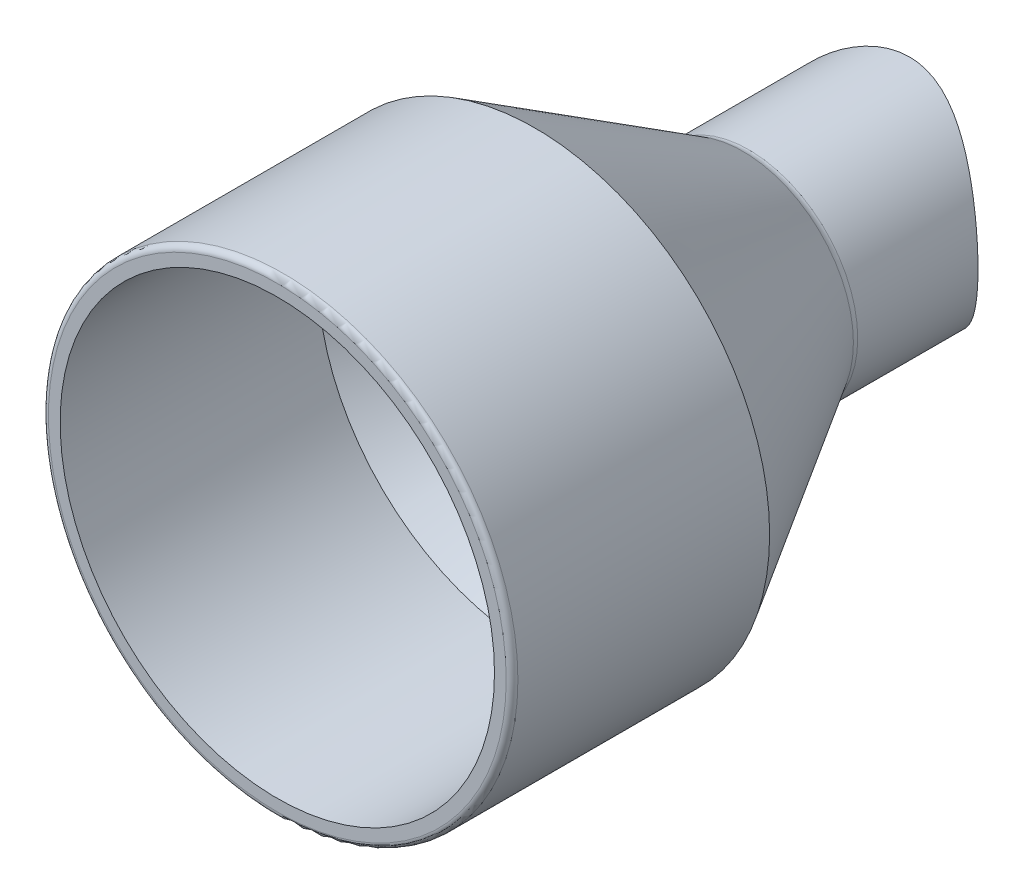
SolidWorks part; units mm, degrees
ref_plane "Front Plane" through (0, 0, 0) normal (0, 0, 1) x (1, 0, 0)
ref_plane "Top Plane" through (0, 0, 0) normal (0, 1, 0) x (1, 0, 0)
ref_plane "Right Plane" through (0, 0, 0) normal (1, 0, 0) x (0, 0, -1)
sketch "Sketch1" plane through (0, 0, 0) normal (0, 0, 1) x (1, 0, 0)
  circle A0 centre (0, 0) radius 20.05
  circle A1 centre (0, 0) radius 18.55
  dimension "D1" = 40.1
  dimension "D2" = 1.5
extrude "Boss-Extrude1" add sketch "Sketch1" along normal blind 22
sketch "Sketch2" plane through (0, 0, 0) normal (0, 0, -1) x (-1, 0, 0)
  circle A0 centre (0, 0) radius 20.05 construction
  point P0 (0, 0)
  point P1 (0, 20.05)
sketch "Sketch4" plane through (0, 0, 22) normal (0, 0, 1) x (1, 0, 0)
  point P0 (0, 20.05)
ref_plane "Plane1" through (0, 0, 0) normal (1, 0, 0) x (0, 0, -1)
sketch "Sketch5" plane through (0, 0, 0) normal (1, 0, 0) x (0, 0, -1)
  line L0 (0, 0) -> (30, 0) construction
  line L3 (18, 9.3) -> (0, 20.05)
  line L4 (0, -20.05) -> (0, 20.05) construction
  line L5 (0, 20.05) -> (0, 18.55)
  line L6 (0, 18.55) -> (18, 7.8)
  line L7 (18, 7.8) -> (18, 9.3)
  line L10 (18, 9.3) -> (32, 9.3)
  line L11 (18, 9.3) -> (18, 7.8)
  line L12 (18, 7.8) -> (32, 7.8)
  line L13 (32, 9.3) -> (32, 7.8)
  dimension "D1" = 18
  dimension "D2" = 14
  dimension "D4" = 1.5
  dimension "5.9" = 7.8
fillet "Fillet1" radius 0.5 1 edges at (20.05, 0, 22)
revolve "Revolve1" add sketch "Sketch5" angle 360 about L0 region at (0, 13.925, -9) region at (0, 8.55, -25)
sketch "Sketch6" plane through (0, 0, 0) normal (1, 0, 0) x (0, 0, -1)
  line L2 (32, 9.3) -> (32, -9.3) construction
  circle A0 centre (42.7969, 0) radius 14.25
  point P5 (32, 0)
  dimension "D1" = 28.5
extrude "Cut-Extrude1" cut sketch "Sketch6" against normal blind 10 and the other way blind 10
sketch "Sketch7" plane through (0, 0, 22) normal (0, 0, 1) x (1, 0, 0)
  line L1 (-6.3, -1) -> (-9.3, -1)
  line L2 (-6.3, -1) -> (-6.3, 1)
  line L3 (-6.3, 1) -> (-9.3, 1)
  line L4 (-9.3, -1) -> (-9.3, 1)
  line L5 (-6.3, -1) -> (-9.3, 1) construction
  line L6 (-6.3, 1) -> (-9.3, -1) construction
  line L7 (6.3, -1) -> (9.3, -1)
  line L8 (6.3, -1) -> (6.3, 1)
  line L9 (6.3, 1) -> (9.3, 1)
  line L10 (9.3, -1) -> (9.3, 1)
  line L11 (6.3, -1) -> (9.3, 1) construction
  line L12 (6.3, 1) -> (9.3, -1) construction
  circle A0 centre (0, 0) radius 9.3 construction
  circle A1 centre (0, 0) radius 9.3
  point P0 (-7.8, 0)
  point P5 (7.8, 0)
  dimension "D1" = 3
  dimension "D2" = 3
  dimension "D3" = 2
  dimension "D4" = 2
extrude "Boss-Extrude2" add sketch "Sketch7" against normal blind 6 from offset 40 contours L3 A1 L1 L2 | A1 L9 L8 L7 region at (-7.7911, 0, 22) region at (7.7911, 0, 22) offset against normal yes
chamfer "Chamfer1" distance 1 angle 45 2 edges at (-6.3, 0, -24) (6.3, 0, -24)
fillet "Fillet2" radius 1 2 edges at (0, -7.8, -18) (0, 7.8, -18)
fillet "Fillet3" radius 1 2 edges at (6.3, 0, -18) (-6.3, 0, -18)
fillet "Fillet4" radius 1 1 edges at (9.3, 0, -18)
